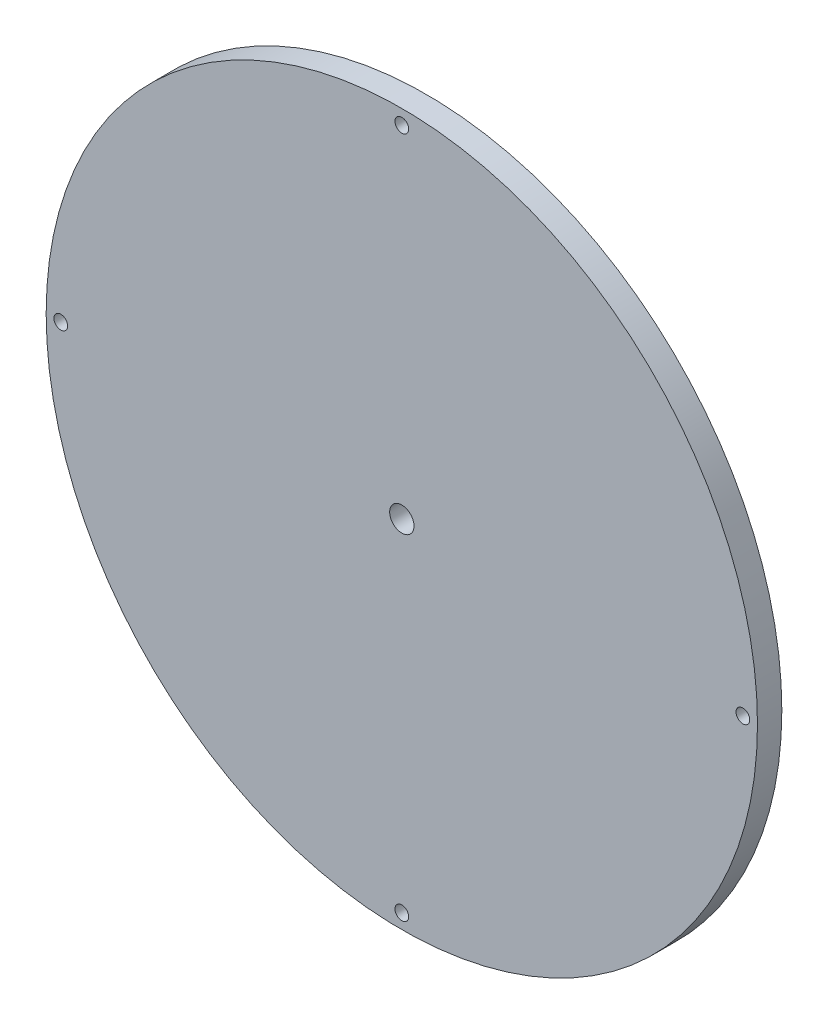
SolidWorks part; units mm, degrees
ref_plane "Front Plane" through (0, 0, 0) normal (0, 0, 1) x (1, 0, 0)
ref_plane "Top Plane" through (0, 0, 0) normal (0, 1, 0) x (1, 0, 0)
ref_plane "Right Plane" through (0, 0, 0) normal (1, 0, 0) x (0, 0, -1)
sketch "Sketch1" plane through (0, 0, 0) normal (0, 0, 1) x (1, 0, 0)
  line L0 (0, 88.9) -> (0, 0) construction
  line L1 (-88.9, 0) -> (0, 0) construction
  circle A0 centre (0, 0) radius 92.71
  circle A5 centre (0, 0) radius 3.175
  circle A6 centre (0, 88.9) radius 1.7859
  circle A7 centre (88.9, 0) radius 1.7859
  circle A8 centre (0, -88.9) radius 1.7859
  circle A9 centre (-88.9, 0) radius 1.7859
  point P14 (0, 0)
  point P16 (0, 0)
  dimension "D1" = 185.42
  dimension "D2" = 6.35
  dimension "D3" = 3.5719
  dimension "D5" = 4
  dimension "D4" = 88.9
  dimension "D6" = 88.9
extrude "Boss-Extrude1" add sketch "Sketch1" along normal blind 6.35 contours A0 region at (-92.4478, 0, 0)
